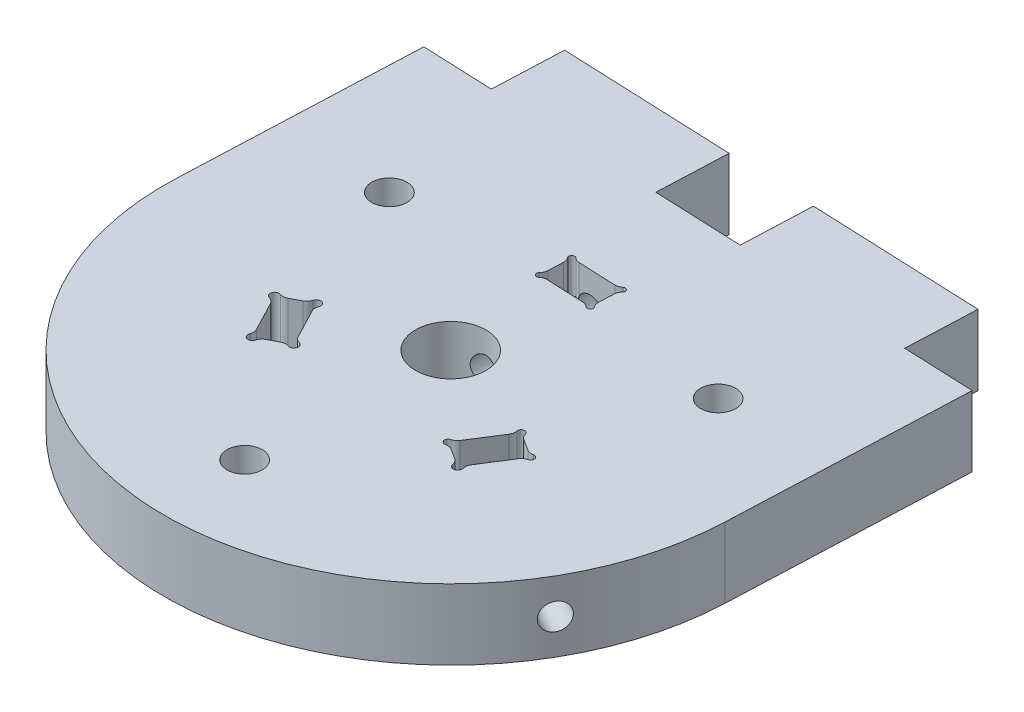
SolidWorks part; units mm, degrees
ref_plane "Front Plane" through (0, 0, 0) normal (0, 0, 1) x (1, 0, 0)
ref_plane "Top Plane" through (0, 0, 0) normal (0, 1, 0) x (1, 0, 0)
ref_plane "Right Plane" through (0, 0, 0) normal (1, 0, 0) x (0, 0, -1)
sketch "Sketch1" plane through (0, 0, 0) normal (0, 1, 0) x (1, 0, 0)
  line L0 (-9.9657, -5.2199) -> (-10.8515, -5.6839)
  line L1 (-19.0068, 12.0412) -> (-0.9246, -22.481)
  line L8 (-9.9657, -5.2199) -> (-28.7898, -15.0797)
  line L9 (-10.8515, -5.6839) -> (-9.4596, -8.3414)
  line L10 (-9.4596, -8.3414) -> (-12.56, -9.9654)
  line L11 (-12.56, -9.9654) -> (-15.344, -4.6503)
  line L12 (-15.344, -4.6503) -> (-12.2435, -3.0264)
  line L13 (-12.2435, -3.0264) -> (-10.8515, -5.6839)
  line L14 (0.6504, 12.3245) -> (-2.3471, 12.4478)
  line L15 (-2.3471, 12.4478) -> (-2.2032, 15.9449)
  line L16 (-2.2032, 15.9449) -> (3.7917, 15.6983)
  line L17 (3.7917, 15.6983) -> (3.6479, 12.2013)
  line L18 (3.6479, 12.2013) -> (0.6504, 12.3245)
  line L19 (10.4952, -6.6407) -> (12.1007, -4.1064)
  line L20 (12.1007, -4.1064) -> (15.0573, -5.9795)
  line L21 (15.0573, -5.9795) -> (11.8463, -11.048)
  line L22 (11.8463, -11.048) -> (8.8897, -9.1749)
  line L23 (8.8897, -9.1749) -> (10.4952, -6.6407)
  line L24 (0.098, 0) -> (-10.8515, -5.6839) construction
  line L25 (0.098, 0) -> (0.6504, 12.3245) construction
  circle A2 centre (0, 0) radius 32.5
  circle A3 centre (-0.9246, -22.481) radius 2
  circle A4 centre (-19.0068, 12.0412) radius 2
  circle A5 centre (19.9314, 10.4398) radius 2
  circle A6 centre (-9.4596, -8.3414) radius 0.5
  circle A7 centre (0, 0) radius 4
  circle A8 centre (-12.56, -9.9654) radius 0.5
  circle A9 centre (-15.344, -4.6503) radius 0.5
  circle A10 centre (-12.2435, -3.0264) radius 0.5
  circle A11 centre (-2.3471, 12.4478) radius 0.3368
  circle A12 centre (-2.2032, 15.9449) radius 0.3368
  circle A13 centre (3.6479, 12.2013) radius 0.3368
  circle A14 centre (3.7917, 15.6983) radius 0.3368
  circle A15 centre (8.8897, -9.1749) radius 0.4038
  circle A16 centre (11.8463, -11.048) radius 0.5
  circle A17 centre (15.0573, -5.9795) radius 0.4038
  circle A18 centre (12.1007, -4.1064) radius 0.4038
  point P42 (0.098, 0)
  dimension "D1" = 3.5
  dimension "D2" = 90
  dimension "D3" = 65
  dimension "D4" = 3
  dimension "D5" = 8
  dimension "D9" = 90
  dimension "D14" = 1
  dimension "D7" = 4
  dimension "D6" = 22.5
  dimension "20" = 22.5
  dimension "D8" = 22.5
  dimension "D10" = 90
  dimension "D11" = 3
  dimension "D12" = 3
  dimension "D13" = 1
  dimension "D16" = 120
  dimension "D15" = 3
extrude "Boss-Extrude2" add sketch "Sketch1" along normal blind 8 contours A10 L13 A4 A3 L9 A6 L10 A8 L11 A2 A9 L12 A18 L20 A17 L21 A16 L22 A15 L23 L19 A14 L17 A13 L18 L14 A11 L15 A12 L16 A7 A5 region at (-7.5451, 0, -30.6662)
fillet "Fillet4" radius 1 24 edges at (-14.901, 4, 4.4183) (-12.0115, 4, 3.4693) (-12.6864, 4, 3.2584) (-15.112, 4, 5.0932) (-12.792, 4, 9.5224) (-12.1171, 4, 9.7334) (-9.9025, 4, 8.5734) (-9.6916, 4, 7.8985) (11.4239, 4, 10.7804) (12.1139, 4, 10.6256) (9.1058, 4, 8.8338) (9.2308, 4, 9.391) (14.8412, 4, 6.3206) (14.7162, 4, 5.7634) (12.4418, 4, 4.3225) (11.8846, 4, 4.4475) (3.6617, 4, -12.5377) (3.3114, 4, -12.2151) (-2.0106, 4, -12.434) (-2.3332, 4, -12.7843) (-2.2171, 4, -15.6084) (-1.8668, 4, -15.931) (3.4552, 4, -15.7121) (3.7779, 4, -15.3618)
sketch "Sketch3" plane through (0, 8, 0) normal (0, 1, 0) x (1, 0, 0)
  circle A0 centre (0, 0) radius 32.5 construction
  point P0 (0, 32.5)
ref_plane "Plane1" through (0, 8, -32.5) normal (0, 0, -1) x (-1, 0, 0)
sketch "Sketch4" plane through (0, 8, -32.5) normal (0, 0, -1) x (-1, 0, 0)
  line L0 (0, 0) -> (0, -8)
  line L1 (32.5, 0) -> (-32.5, 0) construction
  circle A0 centre (0, -4) radius 1.5
extrude "Cut-Extrude1" cut sketch "Sketch4" against normal blind 29 contours A0
pattern_circular "CirPattern1" count 3 over 360 about axis through (0, 8, 0) along (0, 1, 0) of "Cut-Extrude1"
sketch "Sketch6" plane through (0, 0, 0) normal (0, -1, 0) x (1, 0, 0)
  line L0 (-19.0068, -12.0412) -> (19.9314, -10.4398)
  line L1 (32.4725, 1.3355) -> (33.9108, -33.6349)
  line L2 (33.9108, -33.6349) -> (-31.0343, -36.306)
  line L3 (-31.0343, -36.306) -> (-32.4725, -1.3355)
  circle A2 centre (0, 0) radius 32.5 construction
  circle A3 centre (0, 0) radius 4 construction
  circle A4 centre (0, 0) radius 32.5
  dimension "D1" = 35
extrude "Boss-Extrude3" add sketch "Sketch6" against normal blind 8 contours A4 L3 L2 L1 region at (32.4292, 0, -16.1811)
sketch "Sketch9" plane through (1.4383, 0, -34.9704) normal (0.0411, 0, -0.9992) x (-0.9992, 0, -0.0411)
  line L0 (0, 8) -> (5, 8)
  line L1 (32.5, 8) -> (24.5, 8)
  line L2 (32.5, 8) -> (32.5, 0)
  line L3 (32.5, 0) -> (24.5, 0)
  line L4 (24.5, 8) -> (24.5, 0)
  line L5 (-32.5, 8) -> (-24.5, 8)
  line L6 (-32.5, 8) -> (-32.5, 0)
  line L7 (-32.5, 0) -> (-24.5, 0)
  line L8 (-24.5, 8) -> (-24.5, 0)
  line L9 (-32.5, 8) -> (32.5, 8) construction
  line L10 (5, 8) -> (5, 0)
  line L11 (5, 0) -> (-5, 0)
  line L12 (-5, 0) -> (-5, 8)
  line L13 (-5, 8) -> (0, 8)
  dimension "D1" = 8
  dimension "D2" = 8
  dimension "D3" = 8
  dimension "D4" = 10
extrude "Cut-Extrude2" cut sketch "Sketch9" against normal blind 8
